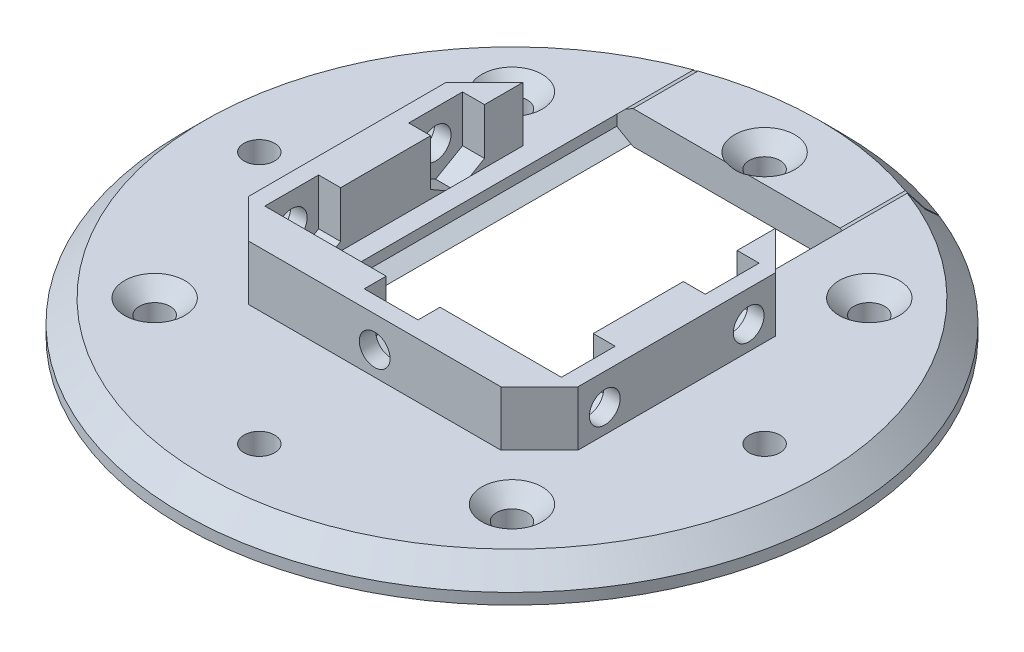
SolidWorks part; units mm, degrees
ref_plane "Front Plane" through (0, 0, 0) normal (0, 0, 1) x (1, 0, 0)
ref_plane "Top Plane" through (0, 0, 0) normal (0, 1, 0) x (1, 0, 0)
ref_plane "Right Plane" through (0, 0, 0) normal (1, 0, 0) x (0, 0, -1)
sketch "Sketch1" plane through (0, 0, 0) normal (0, 1, 0) x (1, 0, 0)
  circle A0 centre (0, 0) radius 30
  dimension "D1" = 60
extrude "Boss-Extrude1" add sketch "Sketch1" along normal mid plane 3
sketch "Sketch2" plane through (0, 1.5, 0) normal (0, 1, 0) x (1, 0, 0)
  line L0 (-11.025, 7.55) -> (-11.025, 30)
  line L1 (-11.025, -7.55) -> (11.025, -7.55)
  line L2 (-11.025, -7.55) -> (-11.025, 7.55)
  line L3 (-11.025, 7.55) -> (11.025, 7.55) construction
  line L4 (11.025, -7.55) -> (11.025, 7.55)
  line L5 (-11.025, -7.55) -> (11.025, 7.55) construction
  line L6 (-11.025, 7.55) -> (11.025, -7.55) construction
  line L7 (-11.025, 30) -> (11.025, 30)
  line L8 (11.025, 30) -> (11.025, 7.55)
  circle A0 centre (0, 0) radius 30 construction
  point P0 (0, 0)
  dimension "D1" = 7.55
  dimension "D2" = 22.05
extrude "Cut-Extrude1" cut sketch "Sketch2" against normal through all
sketch "Sketch3" plane through (0, 0, 7.55) normal (0, 0, -1) x (-1, 0, 0)
  line L0 (0, -1.5) -> (0, 1.5) construction
  line L1 (11.025, -1.5) -> (-11.025, -1.5) construction
  line L2 (11.025, 1.5) -> (-11.025, 1.5) construction
  line L3 (-11.525, -1.5) -> (-9.726, -1.5)
  line L5 (-9.726, -1.5) -> (-11.025, -0.75)
  line L6 (-11.025, -1.5) -> (-11.025, 1.5) construction
  line L7 (-11.025, -0.75) -> (-11.025, 0.75)
  line L8 (-11.025, 0.75) -> (-9.726, 1.5)
  line L9 (-9.726, 1.5) -> (-11.525, 1.5)
  line L10 (30, 1.5) -> (-30, 1.5) construction
  line L11 (-11.525, 1.5) -> (-11.525, -1.5)
  line L12 (-30, -1.5) -> (30, -1.5) construction
  line L13 (-11.025, -1.5) -> (-11.025, 1.5) construction
  line L21 (11.525, 1.5) -> (11.525, -1.5)
  line L22 (9.726, 1.5) -> (11.525, 1.5)
  line L23 (11.025, 0.75) -> (9.726, 1.5)
  line L24 (11.025, -0.75) -> (11.025, 0.75)
  line L25 (9.726, -1.5) -> (11.025, -0.75)
  line L26 (11.525, -1.5) -> (9.726, -1.5)
  point P10 (-11.025, 0)
  dimension "D1" = 0.5
  dimension "D2" = 60
  dimension "D3" = 1.5
extrude "Boss-Extrude2" add sketch "Sketch3" along normal up to surface (35.2479 mm away) up to face at (0, 0, 1.0496)
chamfer "Chamfer1" distance 2 angle 45 1 edges at (0, 1.5, 30)
ref_plane "Plane1" through (0, 0, -20.45) normal (0, 0, -1) x (-1, 0, 0)
sketch "Sketch6" plane through (0, 0, -20.45) normal (0, 0, -1) x (-1, 0, 0)
  line L0 (-9.726, -1.5) -> (-11.025, -0.75) construction
  line L1 (-11.025, -0.75) -> (-11.025, 0.75) construction
  line L2 (-11.025, 0.75) -> (-9.726, 1.5) construction
  line L3 (-9.726, -1.5) -> (-11.025, -0.75) construction
  line L4 (-11.025, -0.75) -> (-11.025, 0.75) construction
  line L5 (-11.025, 0.75) -> (-9.726, 1.5) construction
  line L6 (-9.426, 1.5) -> (-10.875, 0.6634)
  line L7 (9.726, 1.5) -> (-9.726, 1.5) construction
  line L8 (-10.875, 0.6634) -> (-10.875, -0.6634)
  line L9 (-10.875, -0.6634) -> (-9.426, -1.5)
  line L10 (9.726, -1.5) -> (-9.726, -1.5) construction
  line L11 (0, 0) -> (0, 1.5) construction
  line L12 (10.875, -0.6634) -> (9.426, -1.5)
  line L13 (10.875, 0.6634) -> (10.875, -0.6634)
  line L14 (9.426, 1.5) -> (10.875, 0.6634)
  line L15 (-10.875, 0.6634) -> (-10.95, 0.7933) construction
  line L16 (-10.875, 0.6634) -> (-11.025, 0.6634) construction
  line L17 (10.875, -0.6634) -> (9.426, -1.5)
  line L18 (10.875, 0.6634) -> (10.875, -0.6634)
  line L19 (9.426, 1.5) -> (10.875, 0.6634)
  line L20 (-9.426, 1.5) -> (9.426, 1.5)
  line L21 (9.426, -1.5) -> (-9.426, -1.5)
  dimension "D1" = 0.15
extrude "Boss-Extrude3" add sketch "Sketch6" along normal up to surface (7.5095 mm away) separate body contours L21 L12 L13 L14 L20 L6 L8 L9 region at (0, 0, -20.45) up to face at (0, -0.9161, -8.6828)
chamfer "Chamfer2" distance 2 angle 45 2 edges at (-4.7738, 1.5, -29.6177) (4.7738, 1.5, -29.6177)
sketch "Sketch5" plane through (0, 1.5, 0) normal (0, 1, 0) x (1, 0, 0)
  circle A0 centre (0, 0) radius 23 construction
  circle A1 centre (0, 23) radius 1.4
  circle A2 centre (16.2635, 16.2635) radius 1.4
  circle A3 centre (23, 0) radius 1.4
  circle A4 centre (16.2635, -16.2635) radius 1.4
  circle A5 centre (0, -23) radius 1.4
  circle A6 centre (-16.2635, -16.2635) radius 1.4
  circle A7 centre (-23, 0) radius 1.4
  circle A8 centre (-16.2635, 16.2635) radius 1.4
  point P21 (0, 0)
  dimension "D1" = 46
  dimension "D2" = 2.8
  dimension "D3" = 8
extrude "Cut-Extrude2" cut sketch "Sketch5" against normal through all
hole_wizard "CSK for M2.5 Flat Head Machine Screw1" positions "Sketch7" profile "Sketch8" countersink size "M2.5" standard "ANSI Metric" end condition through all
sketch "Sketch7" plane through (0, 1.5, 0) normal (0, 1, 0) x (1, 0, 0)
  point P0 (-16.2635, -16.2635)
  point P3 (16.2635, -16.2635)
  point P6 (-16.2635, 16.2635)
  point P9 (16.2635, 16.2635)
  point P13 (0, 23)
sketch "Sketch8" plane through (-16.2635, 1.5, 16.2635) normal (1, 0, 0) x (0, 0, 1)
  line L0 (0, 0) -> (0, 3)
  line L1 (0, 3) -> (1.35, 3)
  line L2 (1.35, 3) -> (1.35, 1.4)
  line L3 (1.35, 1.4) -> (2.75, 0)
  line L5 (2.75, 0) -> (0, 0)
  line L6 (-1.35, 1.4) -> (-2.75, 0) construction
  line L11 (0, -6.35) -> (0, 107.95) construction
  dimension "Thru Hole Dia." = 2.7
  dimension "Thru Hole Depth" = 3
  dimension "Near C'Sink Dia." = 5.5
  dimension "Near C'Sink Angle" = 90
sketch "Sketch10" plane through (0, 1.5, 0) normal (0, 1, 0) x (1, 0, 0)
  line L0 (0, 0) -> (0, -30) construction
  line L1 (15, -12.5) -> (11.5, -12.5) construction
  line L6 (-15, 12.5) -> (-11.5, 12.5) construction
  line L7 (-15, 12.5) -> (-15, -12.5) construction
  line L8 (-15, -12.5) -> (-11.5, -12.5) construction
  line L9 (-11.5, 12.5) -> (-11.5, -12.5) construction
  line L10 (-11.5, -12.5) -> (11.5, -12.5) construction
  line L11 (-11.5, -12.5) -> (-11.5, -9) construction
  line L12 (-11.5, -9) -> (11.5, -9) construction
  line L13 (11.5, -12.5) -> (11.5, -9) construction
  line L14 (11.5, 12.5) -> (11.5, -12.5) construction
  line L15 (15, 12.5) -> (11.5, 12.5) construction
  line L16 (15, 12.5) -> (15, -12.5) construction
  line L17 (0, 0) -> (-11.5, 0) construction
  line L18 (-11.5, -9) -> (-11.5, 12.5)
  line L19 (-11.5, 12.5) -> (-15, 12.5)
  line L20 (-15, 12.5) -> (-15, -12.5)
  line L21 (-15, -12.5) -> (15, -12.5)
  line L22 (15, -12.5) -> (15, 12.5)
  line L23 (15, 12.5) -> (11.5, 12.5)
  line L24 (11.5, 12.5) -> (11.5, -9)
  line L25 (11.5, -9) -> (-11.5, -9)
  arc A0 (-11.025, 27.9007) -> (11.025, 27.9007) centre (0, 0) ccw construction
  point P18 (-11.5, 0)
  point P36 (0, -12.5)
  point P37 (0, -9)
  dimension "D5" = 30
  dimension "D1" = 3.5
  dimension "D2" = 3.5
  dimension "D3" = 23
  dimension "D4" = 25
  dimension "D6" = 25
extrude "Boss-Extrude4" add sketch "Sketch10" along normal blind 5
sketch "Sketch11" plane through (0, 0, 9) normal (0, 0, -1) x (-1, 0, 0)
  line L0 (-11.5, 6.5) -> (11.5, 6.5) construction
  line L1 (0, 6.5) -> (-2.45, 5.0855) construction
  line L2 (-2.45, 5.0855) -> (-2.45, 2.2565)
  line L3 (-2.45, 2.2565) -> (0, 0.842)
  line L4 (0, 0.842) -> (2.45, 2.2565)
  line L5 (2.45, 2.2565) -> (2.45, 5.0855)
  line L6 (2.45, 5.0855) -> (0, 6.5) construction
  line L7 (-2.45, 5.0855) -> (-2.45, 6.5)
  line L8 (-2.45, 6.5) -> (2.45, 6.5)
  line L9 (2.45, 6.5) -> (2.45, 5.0855)
  circle A0 centre (0, 3.671) radius 2.45 construction
  dimension "D1" = 4.9
extrude "Cut-Extrude3" cut sketch "Sketch11" against normal blind 2
chamfer "Chamfer3" distance 3.5 angle 45 4 edges at (15, 4, 12.5) (-15, 4, 12.5) (-15, 4, -12.5) (15, 4, -12.5)
sketch "Sketch12" plane through (-11.5, 0, 0) normal (1, 0, 0) x (0, 0, -1)
  line L0 (0, 0) -> (0, 6.5) construction
  line L1 (-9, 6.5) -> (9, 6.5) construction
  line L2 (-9, 5.0855) -> (-9, 6.5)
  line L3 (-6.55, 6.5) -> (-9, 5.0855) construction
  line L4 (-9, 5.0855) -> (-9, 2.2565)
  line L5 (-9, 2.2565) -> (-6.55, 0.842)
  line L6 (-6.55, 0.842) -> (-4.1, 2.2565)
  line L7 (-4.1, 2.2565) -> (-4.1, 5.0855)
  line L8 (-4.1, 5.0855) -> (-6.55, 6.5) construction
  line L9 (-9, 6.5) -> (-4.1, 6.5)
  line L10 (-4.1, 6.5) -> (-4.1, 5.0855)
  line L11 (9, 6.5) -> (4.1, 6.5)
  line L12 (9, 5.0855) -> (9, 6.5)
  line L13 (9, 5.0855) -> (9, 2.2565)
  line L14 (9, 2.2565) -> (6.55, 0.842)
  line L15 (6.55, 0.842) -> (4.1, 2.2565)
  line L16 (4.1, 2.2565) -> (4.1, 5.0855)
  line L17 (4.1, 6.5) -> (4.1, 5.0855)
  line L18 (-9, 6.5) -> (-9, 1.5) construction
  circle A0 centre (-6.55, 3.671) radius 2.45 construction
  dimension "D2" = 4.9
extrude "Cut-Extrude4" cut sketch "Sketch12" against normal blind 2
mirror "Mirror1" about plane through (0, 0, 0) normal (1, 0, 0) of "Cut-Extrude4"
sketch "Sketch13" plane through (0, 0, 11) normal (0, 0, -1) x (-1, 0, 0)
  circle A0 centre (0, 3.671) radius 1.4
  dimension "D1" = 2.8
extrude "Cut-Extrude5" cut sketch "Sketch13" against normal blind 2
sketch "Sketch14" plane through (-15, 0, 0) normal (-1, 0, 0) x (0, 0, 1)
  line L0 (0, 6.5) -> (0, 0) construction
  line L1 (-9, 6.5) -> (9, 6.5) construction
  circle A0 centre (6.55, 3.671) radius 1.4
  circle A1 centre (-6.55, 3.671) radius 1.4
  dimension "D1" = 2.8
extrude "Cut-Extrude6" cut sketch "Sketch14" against normal through all both and the other way through all
equation "\"m2.5 width\"= 4.9mm"
equation "\"D1@Sketch11\"=\"m2.5 width\""
equation "\"D2@Sketch12\"=\"m2.5 width\""
